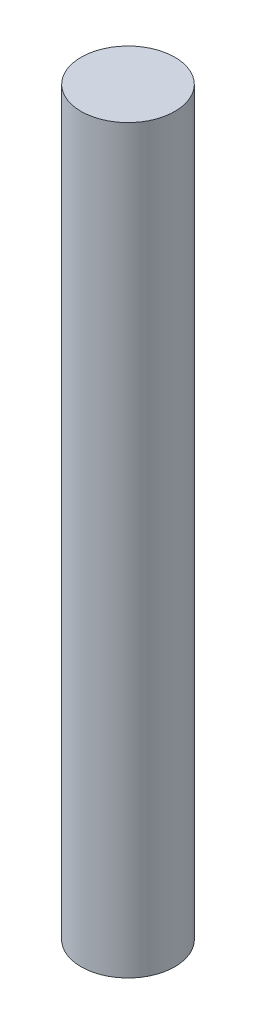
SolidWorks part; units mm, degrees
ref_plane "Front Plane" through (0, 0, 0) normal (0, 0, 1) x (1, 0, 0)
ref_plane "Top Plane" through (0, 0, 0) normal (0, 1, 0) x (1, 0, 0)
ref_plane "Right Plane" through (0, 0, 0) normal (1, 0, 0) x (0, 0, -1)
sketch "Sketch1" plane through (0, 0, 0) normal (0, 1, 0) x (1, 0, 0)
  circle A0 centre (1.9498, -0.2489) radius 4.826
  circle A1 centre (1.9498, -0.2489) radius 4.826 construction
extrude "Boss-Extrude1" add sketch "Sketch1" along normal blind 76.2
